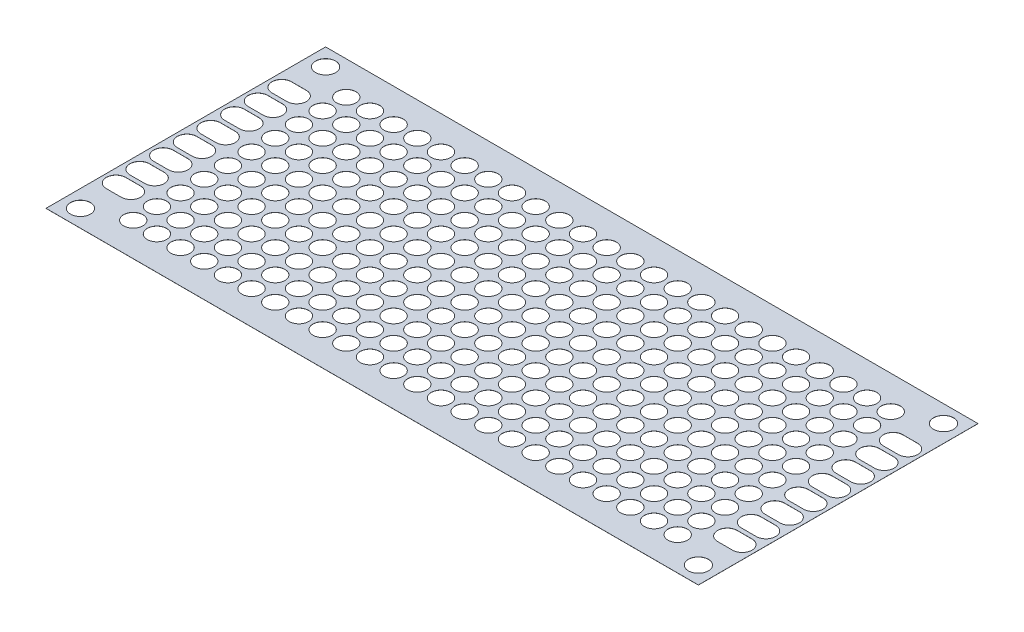
SolidWorks part; units mm, degrees
ref_plane "Front" through (0, 0, 0) normal (0, 0, 1) x (1, 0, 0)
ref_plane "Top" through (0, 0, 0) normal (0, 1, 0) x (1, 0, 0)
ref_plane "Right" through (0, 0, 0) normal (1, 0, 0) x (0, 0, -1)
sketch "Sketch1" plane through (0, 0, 0) normal (0, 1, 0) x (1, 0, 0)
  line L1 (-35, 15) -> (35, 15)
  line L2 (-35, 15) -> (-35, -15)
  line L3 (-35, -15) -> (35, -15)
  line L4 (35, 15) -> (35, -15)
  line L5 (-35, 15) -> (35, -15) construction
  line L6 (-35, -15) -> (35, 15) construction
  point P0 (0, 0)
extrude "Boss-Extrude1" add sketch "Sketch1" along normal blind 0.01
sketch "Sketch2" plane through (0, 0.01, 0) normal (0, 1, 0) x (1, 0, 0)
  line L0 (0, -18.805) -> (0, 0) construction
  line L1 (0, 0) -> (-42.4545, 0) construction
  line L2 (-33.6, -8.89) -> (-32, -8.89) construction
  line L3 (-33.6, -7.8477) -> (-32, -7.8477)
  line L4 (-33.6, -9.9323) -> (-32, -9.9323)
  line L5 (-33.6, -6.35) -> (-32, -6.35) construction
  line L6 (-33.6, -5.3077) -> (-32, -5.3077)
  line L7 (-33.6, -7.3923) -> (-32, -7.3923)
  line L8 (-33.6, -3.81) -> (-32, -3.81) construction
  line L9 (-33.6, -2.7677) -> (-32, -2.7677)
  line L10 (-33.6, -4.8523) -> (-32, -4.8523)
  line L11 (-33.6, -1.27) -> (-32, -1.27) construction
  line L12 (-33.6, -0.2277) -> (-32, -0.2277)
  line L13 (-33.6, -2.3123) -> (-32, -2.3123)
  line L14 (-33.6, 8.89) -> (-32, 8.89) construction
  line L15 (-33.6, 7.8477) -> (-32, 7.8477)
  line L16 (-33.6, 9.9323) -> (-32, 9.9323)
  line L17 (-33.6, 6.35) -> (-32, 6.35) construction
  line L18 (-33.6, 5.3077) -> (-32, 5.3077)
  line L19 (-33.6, 7.3923) -> (-32, 7.3923)
  line L20 (-33.6, 3.81) -> (-32, 3.81) construction
  line L21 (-33.6, 2.7677) -> (-32, 2.7677)
  line L22 (-33.6, 4.8523) -> (-32, 4.8523)
  line L23 (-33.6, 1.27) -> (-32, 1.27) construction
  line L24 (-33.6, 0.2277) -> (-32, 0.2277)
  line L25 (-33.6, 2.3123) -> (-32, 2.3123)
  line L26 (33.6, -8.89) -> (32, -8.89) construction
  line L27 (33.6, -7.8477) -> (32, -7.8477)
  line L28 (33.6, -9.9323) -> (32, -9.9323)
  line L29 (33.6, -6.35) -> (32, -6.35) construction
  line L30 (33.6, -5.3077) -> (32, -5.3077)
  line L31 (33.6, -7.3923) -> (32, -7.3923)
  line L32 (33.6, -3.81) -> (32, -3.81) construction
  line L33 (33.6, -2.7677) -> (32, -2.7677)
  line L34 (33.6, -4.8523) -> (32, -4.8523)
  line L35 (33.6, -1.27) -> (32, -1.27) construction
  line L36 (33.6, -0.2277) -> (32, -0.2277)
  line L37 (33.6, -2.3123) -> (32, -2.3123)
  line L38 (33.6, 8.89) -> (32, 8.89) construction
  line L39 (33.6, 7.8477) -> (32, 7.8477)
  line L40 (33.6, 9.9323) -> (32, 9.9323)
  line L41 (33.6, 6.35) -> (32, 6.35) construction
  line L42 (33.6, 5.3077) -> (32, 5.3077)
  line L43 (33.6, 7.3923) -> (32, 7.3923)
  line L44 (33.6, 3.81) -> (32, 3.81) construction
  line L45 (33.6, 2.7677) -> (32, 2.7677)
  line L46 (33.6, 4.8523) -> (32, 4.8523)
  line L47 (33.6, 1.27) -> (32, 1.27) construction
  line L48 (33.6, 0.2277) -> (32, 0.2277)
  line L49 (33.6, 2.3123) -> (32, 2.3123)
  circle A0 centre (-29.21, -11.43) radius 1.0375
  circle A1 centre (-26.67, -11.43) radius 1.0375
  circle A2 centre (-24.13, -11.43) radius 1.0375
  circle A3 centre (-21.59, -11.43) radius 1.0375
  circle A4 centre (-19.05, -11.43) radius 1.0375
  circle A5 centre (-16.51, -11.43) radius 1.0375
  circle A6 centre (-13.97, -11.43) radius 1.0375
  circle A7 centre (-11.43, -11.43) radius 1.0375
  circle A8 centre (-8.89, -11.43) radius 1.0375
  circle A9 centre (-6.35, -11.43) radius 1.0375
  circle A10 centre (-3.81, -11.43) radius 1.0375
  circle A11 centre (-1.27, -11.43) radius 1.0375
  circle A12 centre (1.27, -11.43) radius 1.0375
  circle A13 centre (3.81, -11.43) radius 1.0375
  circle A14 centre (6.35, -11.43) radius 1.0375
  circle A15 centre (8.89, -11.43) radius 1.0375
  circle A16 centre (11.43, -11.43) radius 1.0375
  circle A17 centre (13.97, -11.43) radius 1.0375
  circle A18 centre (16.51, -11.43) radius 1.0375
  circle A19 centre (19.05, -11.43) radius 1.0375
  circle A20 centre (21.59, -11.43) radius 1.0375
  circle A21 centre (24.13, -11.43) radius 1.0375
  circle A22 centre (26.67, -11.43) radius 1.0375
  circle A23 centre (29.21, -11.43) radius 1.0375
  circle A24 centre (-29.21, -8.89) radius 1.0375
  circle A25 centre (-26.67, -8.89) radius 1.0375
  circle A26 centre (-24.13, -8.89) radius 1.0375
  circle A27 centre (-21.59, -8.89) radius 1.0375
  circle A28 centre (-19.05, -8.89) radius 1.0375
  circle A29 centre (-16.51, -8.89) radius 1.0375
  circle A30 centre (-13.97, -8.89) radius 1.0375
  circle A31 centre (-11.43, -8.89) radius 1.0375
  circle A32 centre (-8.89, -8.89) radius 1.0375
  circle A33 centre (-6.35, -8.89) radius 1.0375
  circle A34 centre (-3.81, -8.89) radius 1.0375
  circle A35 centre (-1.27, -8.89) radius 1.0375
  circle A36 centre (1.27, -8.89) radius 1.0375
  circle A37 centre (3.81, -8.89) radius 1.0375
  circle A38 centre (6.35, -8.89) radius 1.0375
  circle A39 centre (8.89, -8.89) radius 1.0375
  circle A40 centre (11.43, -8.89) radius 1.0375
  circle A41 centre (13.97, -8.89) radius 1.0375
  circle A42 centre (16.51, -8.89) radius 1.0375
  circle A43 centre (19.05, -8.89) radius 1.0375
  circle A44 centre (21.59, -8.89) radius 1.0375
  circle A45 centre (24.13, -8.89) radius 1.0375
  circle A46 centre (26.67, -8.89) radius 1.0375
  circle A47 centre (29.21, -8.89) radius 1.0375
  circle A48 centre (-29.21, -6.35) radius 1.0375
  circle A49 centre (-26.67, -6.35) radius 1.0375
  circle A50 centre (-24.13, -6.35) radius 1.0375
  circle A51 centre (-21.59, -6.35) radius 1.0375
  circle A52 centre (-19.05, -6.35) radius 1.0375
  circle A53 centre (-16.51, -6.35) radius 1.0375
  circle A54 centre (-13.97, -6.35) radius 1.0375
  circle A55 centre (-11.43, -6.35) radius 1.0375
  circle A56 centre (-8.89, -6.35) radius 1.0375
  circle A57 centre (-6.35, -6.35) radius 1.0375
  circle A58 centre (-3.81, -6.35) radius 1.0375
  circle A59 centre (-1.27, -6.35) radius 1.0375
  circle A60 centre (1.27, -6.35) radius 1.0375
  circle A61 centre (3.81, -6.35) radius 1.0375
  circle A62 centre (6.35, -6.35) radius 1.0375
  circle A63 centre (8.89, -6.35) radius 1.0375
  circle A64 centre (11.43, -6.35) radius 1.0375
  circle A65 centre (13.97, -6.35) radius 1.0375
  circle A66 centre (16.51, -6.35) radius 1.0375
  circle A67 centre (19.05, -6.35) radius 1.0375
  circle A68 centre (21.59, -6.35) radius 1.0375
  circle A69 centre (24.13, -6.35) radius 1.0375
  circle A70 centre (26.67, -6.35) radius 1.0375
  circle A71 centre (29.21, -6.35) radius 1.0375
  circle A72 centre (-29.21, -3.81) radius 1.0375
  circle A73 centre (-26.67, -3.81) radius 1.0375
  circle A74 centre (-24.13, -3.81) radius 1.0375
  circle A75 centre (-21.59, -3.81) radius 1.0375
  circle A76 centre (-19.05, -3.81) radius 1.0375
  circle A77 centre (-16.51, -3.81) radius 1.0375
  circle A78 centre (-13.97, -3.81) radius 1.0375
  circle A79 centre (-11.43, -3.81) radius 1.0375
  circle A80 centre (-8.89, -3.81) radius 1.0375
  circle A81 centre (-6.35, -3.81) radius 1.0375
  circle A82 centre (-3.81, -3.81) radius 1.0375
  circle A83 centre (-1.27, -3.81) radius 1.0375
  circle A84 centre (1.27, -3.81) radius 1.0375
  circle A85 centre (3.81, -3.81) radius 1.0375
  circle A86 centre (6.35, -3.81) radius 1.0375
  circle A87 centre (8.89, -3.81) radius 1.0375
  circle A88 centre (11.43, -3.81) radius 1.0375
  circle A89 centre (13.97, -3.81) radius 1.0375
  circle A90 centre (16.51, -3.81) radius 1.0375
  circle A91 centre (19.05, -3.81) radius 1.0375
  circle A92 centre (21.59, -3.81) radius 1.0375
  circle A93 centre (24.13, -3.81) radius 1.0375
  circle A94 centre (26.67, -3.81) radius 1.0375
  circle A95 centre (29.21, -3.81) radius 1.0375
  circle A96 centre (-29.21, -1.27) radius 1.0375
  circle A97 centre (-26.67, -1.27) radius 1.0375
  circle A98 centre (-24.13, -1.27) radius 1.0375
  circle A99 centre (-21.59, -1.27) radius 1.0375
  circle A100 centre (-19.05, -1.27) radius 1.0375
  circle A101 centre (-16.51, -1.27) radius 1.0375
  circle A102 centre (-13.97, -1.27) radius 1.0375
  circle A103 centre (-11.43, -1.27) radius 1.0375
  circle A104 centre (-8.89, -1.27) radius 1.0375
  circle A105 centre (-6.35, -1.27) radius 1.0375
  circle A106 centre (-3.81, -1.27) radius 1.0375
  circle A107 centre (-1.27, -1.27) radius 1.0375
  circle A108 centre (1.27, -1.27) radius 1.0375
  circle A109 centre (3.81, -1.27) radius 1.0375
  circle A110 centre (6.35, -1.27) radius 1.0375
  circle A111 centre (8.89, -1.27) radius 1.0375
  circle A112 centre (11.43, -1.27) radius 1.0375
  circle A113 centre (13.97, -1.27) radius 1.0375
  circle A114 centre (16.51, -1.27) radius 1.0375
  circle A115 centre (19.05, -1.27) radius 1.0375
  circle A116 centre (21.59, -1.27) radius 1.0375
  circle A117 centre (24.13, -1.27) radius 1.0375
  circle A118 centre (26.67, -1.27) radius 1.0375
  circle A119 centre (29.21, -1.27) radius 1.0375
  circle A120 centre (-29.21, 1.27) radius 1.0375
  circle A121 centre (-26.67, 1.27) radius 1.0375
  circle A122 centre (-24.13, 1.27) radius 1.0375
  circle A123 centre (-21.59, 1.27) radius 1.0375
  circle A124 centre (-19.05, 1.27) radius 1.0375
  circle A125 centre (-16.51, 1.27) radius 1.0375
  circle A126 centre (-13.97, 1.27) radius 1.0375
  circle A127 centre (-11.43, 1.27) radius 1.0375
  circle A128 centre (-8.89, 1.27) radius 1.0375
  circle A129 centre (-6.35, 1.27) radius 1.0375
  circle A130 centre (-3.81, 1.27) radius 1.0375
  circle A131 centre (-1.27, 1.27) radius 1.0375
  circle A132 centre (1.27, 1.27) radius 1.0375
  circle A133 centre (3.81, 1.27) radius 1.0375
  circle A134 centre (6.35, 1.27) radius 1.0375
  circle A135 centre (8.89, 1.27) radius 1.0375
  circle A136 centre (11.43, 1.27) radius 1.0375
  circle A137 centre (13.97, 1.27) radius 1.0375
  circle A138 centre (16.51, 1.27) radius 1.0375
  circle A139 centre (19.05, 1.27) radius 1.0375
  circle A140 centre (21.59, 1.27) radius 1.0375
  circle A141 centre (24.13, 1.27) radius 1.0375
  circle A142 centre (26.67, 1.27) radius 1.0375
  circle A143 centre (29.21, 1.27) radius 1.0375
  circle A144 centre (-29.21, 3.81) radius 1.0375
  circle A145 centre (-26.67, 3.81) radius 1.0375
  circle A146 centre (-24.13, 3.81) radius 1.0375
  circle A147 centre (-21.59, 3.81) radius 1.0375
  circle A148 centre (-19.05, 3.81) radius 1.0375
  circle A149 centre (-16.51, 3.81) radius 1.0375
  circle A150 centre (-13.97, 3.81) radius 1.0375
  circle A151 centre (-11.43, 3.81) radius 1.0375
  circle A152 centre (-8.89, 3.81) radius 1.0375
  circle A153 centre (-6.35, 3.81) radius 1.0375
  circle A154 centre (-3.81, 3.81) radius 1.0375
  circle A155 centre (-1.27, 3.81) radius 1.0375
  circle A156 centre (1.27, 3.81) radius 1.0375
  circle A157 centre (3.81, 3.81) radius 1.0375
  circle A158 centre (6.35, 3.81) radius 1.0375
  circle A159 centre (8.89, 3.81) radius 1.0375
  circle A160 centre (11.43, 3.81) radius 1.0375
  circle A161 centre (13.97, 3.81) radius 1.0375
  circle A162 centre (16.51, 3.81) radius 1.0375
  circle A163 centre (19.05, 3.81) radius 1.0375
  circle A164 centre (21.59, 3.81) radius 1.0375
  circle A165 centre (24.13, 3.81) radius 1.0375
  circle A166 centre (26.67, 3.81) radius 1.0375
  circle A167 centre (29.21, 3.81) radius 1.0375
  circle A168 centre (-29.21, 6.35) radius 1.0375
  circle A169 centre (-26.67, 6.35) radius 1.0375
  circle A170 centre (-24.13, 6.35) radius 1.0375
  circle A171 centre (-21.59, 6.35) radius 1.0375
  circle A172 centre (-19.05, 6.35) radius 1.0375
  circle A173 centre (-16.51, 6.35) radius 1.0375
  circle A174 centre (-13.97, 6.35) radius 1.0375
  circle A175 centre (-11.43, 6.35) radius 1.0375
  circle A176 centre (-8.89, 6.35) radius 1.0375
  circle A177 centre (-6.35, 6.35) radius 1.0375
  circle A178 centre (-3.81, 6.35) radius 1.0375
  circle A179 centre (-1.27, 6.35) radius 1.0375
  circle A180 centre (1.27, 6.35) radius 1.0375
  circle A181 centre (3.81, 6.35) radius 1.0375
  circle A182 centre (6.35, 6.35) radius 1.0375
  circle A183 centre (8.89, 6.35) radius 1.0375
  circle A184 centre (11.43, 6.35) radius 1.0375
  circle A185 centre (13.97, 6.35) radius 1.0375
  circle A186 centre (16.51, 6.35) radius 1.0375
  circle A187 centre (19.05, 6.35) radius 1.0375
  circle A188 centre (21.59, 6.35) radius 1.0375
  circle A189 centre (24.13, 6.35) radius 1.0375
  circle A190 centre (26.67, 6.35) radius 1.0375
  circle A191 centre (29.21, 6.35) radius 1.0375
  circle A192 centre (-29.21, 8.89) radius 1.0375
  circle A193 centre (-26.67, 8.89) radius 1.0375
  circle A194 centre (-24.13, 8.89) radius 1.0375
  circle A195 centre (-21.59, 8.89) radius 1.0375
  circle A196 centre (-19.05, 8.89) radius 1.0375
  circle A197 centre (-16.51, 8.89) radius 1.0375
  circle A198 centre (-13.97, 8.89) radius 1.0375
  circle A199 centre (-11.43, 8.89) radius 1.0375
  circle A200 centre (-8.89, 8.89) radius 1.0375
  circle A201 centre (-6.35, 8.89) radius 1.0375
  circle A202 centre (-3.81, 8.89) radius 1.0375
  circle A203 centre (-1.27, 8.89) radius 1.0375
  circle A204 centre (1.27, 8.89) radius 1.0375
  circle A205 centre (3.81, 8.89) radius 1.0375
  circle A206 centre (6.35, 8.89) radius 1.0375
  circle A207 centre (8.89, 8.89) radius 1.0375
  circle A208 centre (11.43, 8.89) radius 1.0375
  circle A209 centre (13.97, 8.89) radius 1.0375
  circle A210 centre (16.51, 8.89) radius 1.0375
  circle A211 centre (19.05, 8.89) radius 1.0375
  circle A212 centre (21.59, 8.89) radius 1.0375
  circle A213 centre (24.13, 8.89) radius 1.0375
  circle A214 centre (26.67, 8.89) radius 1.0375
  circle A215 centre (29.21, 8.89) radius 1.0375
  circle A216 centre (-29.21, 11.43) radius 1.0375
  circle A217 centre (-26.67, 11.43) radius 1.0375
  circle A218 centre (-24.13, 11.43) radius 1.0375
  circle A219 centre (-21.59, 11.43) radius 1.0375
  circle A220 centre (-19.05, 11.43) radius 1.0375
  circle A221 centre (-16.51, 11.43) radius 1.0375
  circle A222 centre (-13.97, 11.43) radius 1.0375
  circle A223 centre (-11.43, 11.43) radius 1.0375
  circle A224 centre (-8.89, 11.43) radius 1.0375
  circle A225 centre (-6.35, 11.43) radius 1.0375
  circle A226 centre (-3.81, 11.43) radius 1.0375
  circle A227 centre (-1.27, 11.43) radius 1.0375
  circle A228 centre (1.27, 11.43) radius 1.0375
  circle A229 centre (3.81, 11.43) radius 1.0375
  circle A230 centre (6.35, 11.43) radius 1.0375
  circle A231 centre (8.89, 11.43) radius 1.0375
  circle A232 centre (11.43, 11.43) radius 1.0375
  circle A233 centre (13.97, 11.43) radius 1.0375
  circle A234 centre (16.51, 11.43) radius 1.0375
  circle A235 centre (19.05, 11.43) radius 1.0375
  circle A236 centre (21.59, 11.43) radius 1.0375
  circle A237 centre (24.13, 11.43) radius 1.0375
  circle A238 centre (26.67, 11.43) radius 1.0375
  circle A239 centre (29.21, 11.43) radius 1.0375
  circle A240 centre (-33.15, -13.15) radius 1.0742
  circle A241 centre (-33.15, 13.15) radius 1.0742
  circle A242 centre (33.15, 13.15) radius 1.0742
  circle A243 centre (33.15, -13.15) radius 1.0742
  arc A244 (-33.6, -7.8477) -> (-33.6, -9.9323) centre (-33.6, -8.89) ccw
  arc A245 (-32, -9.9323) -> (-32, -7.8477) centre (-32, -8.89) ccw
  arc A246 (-33.6, -5.3077) -> (-33.6, -7.3923) centre (-33.6, -6.35) ccw
  arc A247 (-32, -7.3923) -> (-32, -5.3077) centre (-32, -6.35) ccw
  arc A248 (-33.6, -2.7677) -> (-33.6, -4.8523) centre (-33.6, -3.81) ccw
  arc A249 (-32, -4.8523) -> (-32, -2.7677) centre (-32, -3.81) ccw
  arc A250 (-33.6, -0.2277) -> (-33.6, -2.3123) centre (-33.6, -1.27) ccw
  arc A251 (-32, -2.3123) -> (-32, -0.2277) centre (-32, -1.27) ccw
  arc A252 (-33.6, 7.8477) -> (-33.6, 9.9323) centre (-33.6, 8.89) cw
  arc A253 (-32, 9.9323) -> (-32, 7.8477) centre (-32, 8.89) cw
  arc A254 (-33.6, 5.3077) -> (-33.6, 7.3923) centre (-33.6, 6.35) cw
  arc A255 (-32, 7.3923) -> (-32, 5.3077) centre (-32, 6.35) cw
  arc A256 (-33.6, 2.7677) -> (-33.6, 4.8523) centre (-33.6, 3.81) cw
  arc A257 (-32, 4.8523) -> (-32, 2.7677) centre (-32, 3.81) cw
  arc A258 (-33.6, 0.2277) -> (-33.6, 2.3123) centre (-33.6, 1.27) cw
  arc A259 (-32, 2.3123) -> (-32, 0.2277) centre (-32, 1.27) cw
  arc A260 (33.6, -7.8477) -> (33.6, -9.9323) centre (33.6, -8.89) cw
  arc A261 (32, -9.9323) -> (32, -7.8477) centre (32, -8.89) cw
  arc A262 (33.6, -5.3077) -> (33.6, -7.3923) centre (33.6, -6.35) cw
  arc A263 (32, -7.3923) -> (32, -5.3077) centre (32, -6.35) cw
  arc A264 (33.6, -2.7677) -> (33.6, -4.8523) centre (33.6, -3.81) cw
  arc A265 (32, -4.8523) -> (32, -2.7677) centre (32, -3.81) cw
  arc A266 (33.6, -0.2277) -> (33.6, -2.3123) centre (33.6, -1.27) cw
  arc A267 (32, -2.3123) -> (32, -0.2277) centre (32, -1.27) cw
  arc A268 (33.6, 7.8477) -> (33.6, 9.9323) centre (33.6, 8.89) ccw
  arc A269 (32, 9.9323) -> (32, 7.8477) centre (32, 8.89) ccw
  arc A270 (33.6, 5.3077) -> (33.6, 7.3923) centre (33.6, 6.35) ccw
  arc A271 (32, 7.3923) -> (32, 5.3077) centre (32, 6.35) ccw
  arc A272 (33.6, 2.7677) -> (33.6, 4.8523) centre (33.6, 3.81) ccw
  arc A273 (32, 4.8523) -> (32, 2.7677) centre (32, 3.81) ccw
  arc A274 (33.6, 0.2277) -> (33.6, 2.3123) centre (33.6, 1.27) ccw
  arc A275 (32, 2.3123) -> (32, 0.2277) centre (32, 1.27) ccw
  point P493 (-32.8, -8.89)
  point P501 (-32.8, -6.35)
  point P508 (-32.8, -3.81)
  point P515 (-32.8, -1.27)
  point P521 (-32.8, 8.89)
  point P528 (-32.8, 6.35)
  point P535 (-32.8, 3.81)
  point P542 (-32.8, 1.27)
  point P549 (32.8, -8.89)
  point P556 (32.8, -6.35)
  point P563 (32.8, -3.81)
  point P570 (32.8, -1.27)
  point P577 (32.8, 8.89)
  point P584 (32.8, 6.35)
  point P591 (32.8, 3.81)
  point P598 (32.8, 1.27)
  dimension "D1" = 24
  dimension "D3" = 4
  dimension "D2" = 10
extrude "Cut-Extrude1" cut sketch "Sketch2" against normal through all
